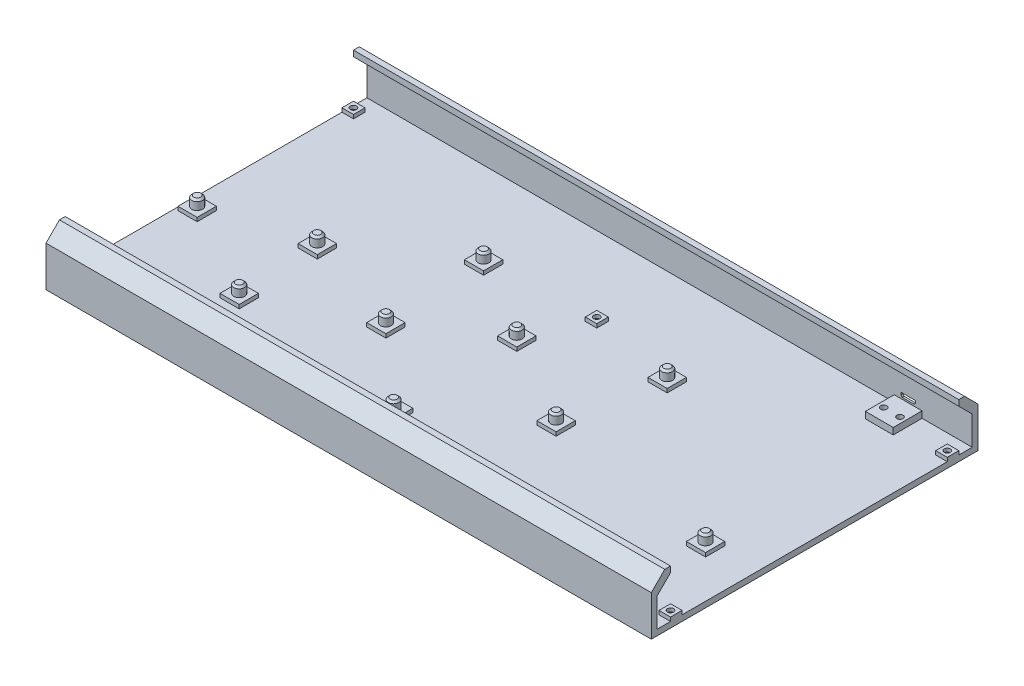
SolidWorks part; units mm, degrees
ref_plane "Front Plane" through (0, 0, 0) normal (0, 0, 1) x (1, 0, 0)
ref_plane "Top Plane" through (0, 0, 0) normal (0, 1, 0) x (1, 0, 0)
ref_plane "Right Plane" through (0, 0, 0) normal (1, 0, 0) x (0, 0, -1)
sketch "Sketch1" plane through (0, 0, 0) normal (0, 1, 0) x (1, 0, 0)
  line L1 (0, 0) -> (315, 0)
  line L2 (0, 0) -> (0, 150)
  line L3 (0, 150) -> (315, 150)
  line L4 (315, 0) -> (315, 150)
  line L5 (157.5, 150) -> (157.5, 0) construction
  line L6 (0, 75) -> (315, 75) construction
  line L7 (11.8793, 83.5932) -> (37.8793, 83.5932)
  line L8 (11.8793, 83.5932) -> (11.8793, 72.5932)
  line L9 (11.8793, 72.5932) -> (37.8793, 72.5932)
  line L10 (37.8793, 83.5932) -> (37.8793, 72.5932)
  line L11 (24.8793, 72.5932) -> (24.8793, 83.5932) construction
  line L12 (11.8793, 78.0932) -> (37.8793, 78.0932) construction
  line L17 (114.9071, 89.45) -> (181.1755, 89.45) construction
  line L18 (65.6251, 144.4154) -> (205.6251, 144.4154)
  line L42 (260.2509, 144.4154) -> (285.2509, 144.4154)
  line L43 (234.1707, 144.4154) -> (259.1707, 144.4154)
  line L44 (234.1707, 144.4154) -> (234.1707, 52.4154)
  line L45 (234.1707, 52.4154) -> (259.1707, 52.4154)
  line L46 (259.1707, 144.4154) -> (259.1707, 52.4154)
  line L47 (246.6707, 52.4154) -> (246.6707, 144.4154) construction
  line L48 (234.1707, 98.4154) -> (259.1707, 98.4154) construction
  line L49 (260.2509, 144.4154) -> (260.2509, 52.4154)
  line L50 (260.2509, 52.4154) -> (285.2509, 52.4154)
  line L51 (285.2509, 144.4154) -> (285.2509, 52.4154)
  line L52 (287.1734, 144.4154) -> (312.1734, 144.4154)
  line L53 (287.1734, 144.4154) -> (287.1734, 52.4154)
  line L54 (287.1734, 52.4154) -> (312.1734, 52.4154)
  line L55 (312.1734, 144.4154) -> (312.1734, 52.4154)
  line L72 (65.6251, 144.4154) -> (65.6251, 124.4154)
  line L73 (65.6251, 124.4154) -> (205.6251, 124.4154)
  line L74 (205.6251, 144.4154) -> (205.6251, 124.4154)
  line L75 (135.6251, 124.4154) -> (135.6251, 144.4154) construction
  line L76 (65.6251, 134.4154) -> (205.6251, 134.4154) construction
  line L81 (65.688, 113.6965) -> (85.688, 113.6965)
  line L82 (65.688, 113.6965) -> (65.688, 33.6965)
  line L83 (10.3843, 23.9694) -> (90.3843, 23.9694)
  line L84 (10.3843, 23.9694) -> (10.3843, 3.9694)
  line L85 (10.3843, 3.9694) -> (90.3843, 3.9694)
  line L86 (90.3843, 23.9694) -> (90.3843, 3.9694)
  line L87 (50.3843, 3.9694) -> (50.3843, 23.9694) construction
  line L88 (10.3843, 13.9694) -> (90.3843, 13.9694) construction
  line L89 (65.688, 33.6965) -> (85.688, 33.6965)
  line L90 (85.688, 113.6965) -> (85.688, 33.6965)
  line L91 (75.688, 33.6965) -> (75.688, 113.6965) construction
  line L92 (65.688, 73.6965) -> (85.688, 73.6965) construction
  line L93 (205.3895, 44.9232) -> (245.3895, 44.9232)
  line L94 (205.3895, 44.9232) -> (205.3895, 4.9232)
  line L95 (205.3895, 4.9232) -> (245.3895, 4.9232)
  line L96 (245.3895, 44.9232) -> (245.3895, 4.9232)
  line L97 (225.3895, 4.9232) -> (225.3895, 44.9232) construction
  line L98 (205.3895, 24.9232) -> (245.3895, 24.9232) construction
  line L99 (245.3895, 44.9232) -> (265.3895, 44.9232)
  line L100 (245.3895, 44.9232) -> (245.3895, 24.9232)
  line L101 (245.3895, 24.9232) -> (265.3895, 24.9232)
  line L102 (265.3895, 44.9232) -> (265.3895, 24.9232)
  line L103 (255.3895, 24.9232) -> (255.3895, 44.9232) construction
  line L104 (245.3895, 34.9232) -> (265.3895, 34.9232) construction
  line L105 (181.1755, 89.45) -> (181.1755, 24.3783) construction
  line L106 (181.1755, 24.3783) -> (114.9071, 24.3783) construction
  line L107 (33.5208, 117.195) -> (33.5208, 48.1962) construction
  line L109 (273.3018, 34.1392) -> (307.3018, 34.1392)
  line L110 (273.3018, 34.1392) -> (273.3018, 8.1392)
  line L111 (273.3018, 8.1392) -> (307.3018, 8.1392)
  line L112 (307.3018, 34.1392) -> (307.3018, 8.1392)
  line L113 (290.3018, 8.1392) -> (290.3018, 34.1392) construction
  line L114 (273.3018, 21.1392) -> (307.3018, 21.1392) construction
  line L115 (117.5413, 65.9142) -> (178.5413, 65.9142)
  line L116 (117.5413, 65.9142) -> (117.5413, 47.9142)
  line L117 (117.5413, 47.9142) -> (178.5413, 47.9142)
  line L118 (178.5413, 65.9142) -> (178.5413, 47.9142)
  line L119 (148.0413, 47.9142) -> (148.0413, 65.9142) construction
  line L120 (117.5413, 56.9142) -> (178.5413, 56.9142) construction
  line L121 (5.8793, 85.7294) -> (45.8793, 85.7294)
  line L122 (5.8793, 85.7294) -> (5.8793, 70.457)
  line L123 (5.8793, 70.457) -> (45.8793, 70.457)
  line L124 (45.8793, 85.7294) -> (45.8793, 70.457)
  line L125 (25.8793, 70.457) -> (25.8793, 85.7294) construction
  line L126 (5.8793, 78.0932) -> (45.8793, 78.0932) construction
  circle A0 centre (33.5208, 117.195) radius 27.5
  circle A1 centre (33.5208, 48.1962) radius 20
  circle A2 centre (114.9071, 24.3783) radius 20
  circle A3 centre (114.9071, 89.45) radius 20
  circle A4 centre (181.1755, 24.3783) radius 20
  circle A5 centre (181.1755, 89.45) radius 20
  point P38 (148.0413, 56.9142)
  point P42 (148.0413, 89.45)
  point P56 (181.1755, 56.9142)
  point P57 (25.8793, 78.0932)
  point P195 (24.8793, 78.0932)
  point P224 (290.3018, 21.1392)
  point P252 (246.6707, 98.4154)
  point P259 (225.3895, 24.9232)
  point P417 (255.3895, 34.9232)
  point P438 (75.688, 73.6965)
  point P456 (157.5, 75)
  point P559 (50.3843, 13.9694)
  point P704 (135.6251, 134.4154)
  dimension "D3" = 55
  dimension "D6" = 40
  dimension "D1" = 150
  dimension "D2" = 315
  dimension "D4" = 26
  dimension "D5" = 11
  dimension "D7" = 20
  dimension "D8" = 140
  dimension "D9" = 25
  dimension "D10" = 92
  dimension "D11" = 20
  dimension "D12" = 80
  dimension "D13" = 20
  dimension "D14" = 80
  dimension "D15" = 40
  dimension "D16" = 40
  dimension "D17" = 20
  dimension "D18" = 34
  dimension "D19" = 26
  dimension "D20" = 61
  dimension "D21" = 18
  dimension "D22" = 6
  dimension "D23" = 8
  dimension "D24" = 25
  dimension "D25" = 25
sketch "Sketch2" plane through (0, 0, 0) normal (0, 1, 0) x (1, 0, 0)
  line L1 (0, 150) -> (6, 150)
  line L2 (0, 150) -> (0, 144)
  line L3 (0, 144) -> (6, 144)
  line L4 (6, 150) -> (6, 144)
  line L5 (3, 144) -> (3, 150) construction
  line L6 (0, 147) -> (6, 147) construction
  line L8 (0, 6) -> (6, 6)
  line L9 (0, 6) -> (0, 0)
  line L10 (0, 0) -> (6, 0)
  line L11 (6, 6) -> (6, 0)
  line L12 (3, 0) -> (3, 6) construction
  line L13 (0, 3) -> (6, 3) construction
  line L25 (157.5848, 119.0301) -> (163.5848, 119.0301)
  line L26 (157.5848, 119.0301) -> (157.5848, 113.0301)
  line L31 (157.5848, 113.0301) -> (163.5848, 113.0301)
  line L32 (163.5848, 119.0301) -> (163.5848, 113.0301)
  line L37 (160.5848, 113.0301) -> (160.5848, 119.0301) construction
  line L38 (157.5848, 116.0301) -> (163.5848, 116.0301) construction
  line L43 (143.8527, 27.0473) -> (153.8527, 27.0473)
  line L44 (143.8527, 27.0473) -> (143.8527, 17.0473)
  line L49 (143.8527, 17.0473) -> (153.8527, 17.0473)
  line L50 (153.8527, 27.0473) -> (153.8527, 17.0473)
  line L55 (148.8527, 17.0473) -> (148.8527, 27.0473) construction
  line L56 (143.8527, 22.0473) -> (153.8527, 22.0473) construction
  line L68 (146.1081, 11.4408) -> (152.1081, 11.4408)
  line L73 (146.1081, 11.4408) -> (146.1081, 5.4408)
  line L74 (103.2441, 63.6402) -> (113.2441, 63.6402)
  line L75 (309, 6) -> (315, 6)
  line L76 (309, 6) -> (309, 0)
  line L77 (309, 0) -> (315, 0)
  line L78 (315, 6) -> (315, 0)
  line L79 (312, 0) -> (312, 6) construction
  line L80 (309, 3) -> (315, 3) construction
  line L85 (103.2441, 63.6402) -> (103.2441, 53.6402)
  line L86 (103.2441, 53.6402) -> (113.2441, 53.6402)
  line L87 (309, 150) -> (315, 150)
  line L88 (309, 150) -> (309, 144)
  line L89 (309, 144) -> (315, 144)
  line L90 (315, 150) -> (315, 144)
  line L91 (312, 144) -> (312, 150) construction
  line L92 (309, 147) -> (315, 147) construction
  line L93 (113.2441, 63.6402) -> (113.2441, 53.6402)
  line L94 (108.2441, 53.6402) -> (108.2441, 63.6402) construction
  line L95 (103.2441, 58.6402) -> (113.2441, 58.6402) construction
  line L96 (49.7601, 81.4098) -> (59.7601, 81.4098)
  line L97 (49.7601, 81.4098) -> (49.7601, 71.4098)
  line L98 (49.7601, 71.4098) -> (59.7601, 71.4098)
  line L99 (59.7601, 81.4098) -> (59.7601, 71.4098)
  line L100 (54.7601, 71.4098) -> (54.7601, 81.4098) construction
  line L101 (49.7601, 76.4098) -> (59.7601, 76.4098) construction
  line L102 (51.8887, 38.6479) -> (61.8887, 38.6479)
  line L103 (51.8887, 38.6479) -> (51.8887, 28.6479)
  line L104 (51.8887, 28.6479) -> (61.8887, 28.6479)
  line L105 (61.8887, 38.6479) -> (61.8887, 28.6479)
  line L106 (56.8887, 28.6479) -> (56.8887, 38.6479) construction
  line L107 (51.8887, 33.6479) -> (61.8887, 33.6479) construction
  line L108 (1.6875, 66.969) -> (11.6875, 66.969)
  line L109 (1.6875, 66.969) -> (1.6875, 56.969)
  line L110 (1.6875, 56.969) -> (11.6875, 56.969)
  line L111 (11.6875, 66.969) -> (11.6875, 56.969)
  line L112 (6.6875, 56.969) -> (6.6875, 66.969) construction
  line L113 (1.6875, 61.969) -> (11.6875, 61.969) construction
  line L114 (100.3283, 117.374) -> (110.3283, 117.374)
  line L115 (100.3283, 117.374) -> (100.3283, 107.374)
  line L116 (100.3283, 107.374) -> (110.3283, 107.374)
  line L117 (110.3283, 117.374) -> (110.3283, 107.374)
  line L118 (105.3283, 107.374) -> (105.3283, 117.374) construction
  line L119 (100.3283, 112.374) -> (110.3283, 112.374) construction
  line L120 (191.7316, 63.7001) -> (201.7316, 63.7001)
  line L121 (191.7316, 63.7001) -> (191.7316, 53.7001)
  line L122 (191.7316, 53.7001) -> (201.7316, 53.7001)
  line L123 (201.7316, 63.7001) -> (201.7316, 53.7001)
  line L124 (196.7316, 53.7001) -> (196.7316, 63.7001) construction
  line L125 (191.7316, 58.7001) -> (201.7316, 58.7001) construction
  line L130 (146.1081, 5.4408) -> (152.1081, 5.4408)
  line L131 (152.1081, 11.4408) -> (152.1081, 5.4408)
  line L132 (255.4879, 16.7818) -> (265.4879, 16.7818)
  line L133 (255.4879, 16.7818) -> (255.4879, 6.7818)
  line L134 (255.4879, 6.7818) -> (265.4879, 6.7818)
  line L135 (265.4879, 16.7818) -> (265.4879, 6.7818)
  line L136 (260.4879, 6.7818) -> (260.4879, 16.7818) construction
  line L137 (255.4879, 11.7818) -> (265.4879, 11.7818) construction
  line L138 (285.0588, 48.1735) -> (295.0588, 48.1735)
  line L139 (285.0588, 48.1735) -> (285.0588, 38.1735)
  line L140 (285.0588, 38.1735) -> (295.0588, 38.1735)
  line L141 (295.0588, 48.1735) -> (295.0588, 38.1735)
  line L142 (290.0588, 38.1735) -> (290.0588, 48.1735) construction
  line L143 (285.0588, 43.1735) -> (295.0588, 43.1735) construction
  line L144 (143.296, 91.7052) -> (153.296, 91.7052)
  line L145 (143.296, 91.7052) -> (143.296, 81.7052)
  line L146 (143.296, 81.7052) -> (153.296, 81.7052)
  line L147 (153.296, 91.7052) -> (153.296, 81.7052)
  line L148 (148.296, 81.7052) -> (148.296, 91.7052) construction
  line L149 (143.296, 86.7052) -> (153.296, 86.7052) construction
  line L150 (201.1129, 112.1386) -> (211.1129, 112.1386)
  line L151 (201.1129, 112.1386) -> (201.1129, 102.1386)
  line L152 (201.1129, 102.1386) -> (211.1129, 102.1386)
  line L153 (211.1129, 112.1386) -> (211.1129, 102.1386)
  line L154 (206.1129, 102.1386) -> (206.1129, 112.1386) construction
  line L155 (201.1129, 107.1386) -> (211.1129, 107.1386) construction
  line L156 (149.1081, 5.4408) -> (149.1081, 11.4408) construction
  line L157 (146.1081, 8.4408) -> (152.1081, 8.4408) construction
  circle A0 centre (3, 147) radius 1.6
  circle A1 centre (3, 3) radius 1.6
  circle A12 centre (312, 3) radius 1.6
  circle A14 centre (312, 147) radius 1.6
  circle A16 centre (160.5848, 116.0301) radius 1.6
  circle A17 centre (148.8527, 22.0473) radius 3
  circle A19 centre (108.2441, 58.6402) radius 3
  circle A20 centre (54.7601, 76.4098) radius 3
  circle A21 centre (56.8887, 33.6479) radius 3
  circle A22 centre (6.6875, 61.969) radius 3
  circle A23 centre (105.3283, 112.374) radius 3
  circle A24 centre (196.7316, 58.7001) radius 3
  circle A26 centre (260.4879, 11.7818) radius 3
  circle A27 centre (290.0588, 43.1735) radius 3
  circle A28 centre (148.296, 86.7052) radius 3
  circle A29 centre (206.1129, 107.1386) radius 3
  circle A30 centre (149.1081, 8.4408) radius 1.6
  dimension "D1" = 3.2
  dimension "D4" = 3.2
  dimension "D6" = 3.2
  dimension "D8" = 3.2
  dimension "D9" = 3.2
  dimension "D12" = 6
  dimension "D15" = 6
  dimension "D18" = 3.2
  dimension "D2" = 6
  dimension "D3" = 6
  dimension "D5" = 6
  dimension "D7" = 6
  dimension "D10" = 6
  dimension "D11" = 6
  dimension "D13" = 10
  dimension "D14" = 10
  dimension "D16" = 10
  dimension "D17" = 10
  dimension "D19" = 6
sketch "Sketch3" plane through (0, 0, 0) normal (0, 1, 0) x (1, 0, 0)
  line L0 (0, 0) -> (0, 150) construction
  line L1 (0, 160) -> (315, 160)
  line L2 (0, 160) -> (0, -10)
  line L3 (0, -10) -> (315, -10)
  line L4 (315, 160) -> (315, -10)
  line L5 (157.5, -10) -> (157.5, 160) construction
  line L6 (0, 75) -> (315, 75) construction
  line L7 (315, 0) -> (315, 150) construction
  line L8 (0, 150) -> (315, 150) construction
  line L9 (0, 0) -> (315, 0) construction
  point P408 (157.5, 75)
  dimension "D1" = 10
  dimension "D2" = 10
extrude "Boss-Extrude1" add sketch "Sketch3" along normal blind 3
sketch "Sketch5" plane through (0, 3, 0) normal (0, 1, 0) x (1, 0, 0)
  line L1 (0, 150) -> (6, 150)
  line L2 (0, 150) -> (0, 144)
  line L3 (0, 144) -> (6, 144)
  line L4 (6, 150) -> (6, 144)
  line L5 (3, 144) -> (3, 150) construction
  line L6 (0, 147) -> (6, 147) construction
  line L7 (6, 0) -> (0, 0)
  line L8 (6, 0) -> (6, 6)
  line L9 (6, 6) -> (0, 6)
  line L10 (0, 0) -> (0, 6)
  line L11 (3, 6) -> (3, 0) construction
  line L12 (6, 3) -> (0, 3) construction
  line L13 (1.6875, 66.969) -> (11.6875, 66.969)
  line L14 (1.6875, 66.969) -> (1.6875, 56.969)
  line L15 (1.6875, 56.969) -> (11.6875, 56.969)
  line L16 (11.6875, 66.969) -> (11.6875, 56.969)
  line L17 (6.6875, 56.969) -> (6.6875, 66.969) construction
  line L18 (1.6875, 61.969) -> (11.6875, 61.969) construction
  line L19 (49.7601, 81.4098) -> (59.7601, 81.4098)
  line L20 (49.7601, 81.4098) -> (49.7601, 71.4098)
  line L21 (49.7601, 71.4098) -> (59.7601, 71.4098)
  line L22 (59.7601, 81.4098) -> (59.7601, 71.4098)
  line L23 (54.7601, 71.4098) -> (54.7601, 81.4098) construction
  line L24 (49.7601, 76.4098) -> (59.7601, 76.4098) construction
  line L25 (51.8887, 38.6479) -> (61.8887, 38.6479)
  line L26 (51.8887, 38.6479) -> (51.8887, 28.6479)
  line L27 (51.8887, 28.6479) -> (61.8887, 28.6479)
  line L28 (61.8887, 38.6479) -> (61.8887, 28.6479)
  line L29 (56.8887, 28.6479) -> (56.8887, 38.6479) construction
  line L30 (51.8887, 33.6479) -> (61.8887, 33.6479) construction
  line L31 (100.3283, 117.374) -> (110.3283, 117.374)
  line L32 (100.3283, 117.374) -> (100.3283, 107.374)
  line L33 (100.3283, 107.374) -> (110.3283, 107.374)
  line L34 (110.3283, 117.374) -> (110.3283, 107.374)
  line L35 (105.3283, 107.374) -> (105.3283, 117.374) construction
  line L36 (100.3283, 112.374) -> (110.3283, 112.374) construction
  line L37 (103.2441, 63.6402) -> (113.2441, 63.6402)
  line L38 (103.2441, 63.6402) -> (103.2441, 53.6402)
  line L39 (103.2441, 53.6402) -> (113.2441, 53.6402)
  line L40 (113.2441, 63.6402) -> (113.2441, 53.6402)
  line L41 (108.2441, 53.6402) -> (108.2441, 63.6402) construction
  line L42 (103.2441, 58.6402) -> (113.2441, 58.6402) construction
  line L43 (143.296, 91.7052) -> (153.296, 91.7052)
  line L44 (143.296, 91.7052) -> (143.296, 81.7052)
  line L45 (143.296, 81.7052) -> (153.296, 81.7052)
  line L46 (153.296, 91.7052) -> (153.296, 81.7052)
  line L47 (148.296, 81.7052) -> (148.296, 91.7052) construction
  line L48 (143.296, 86.7052) -> (153.296, 86.7052) construction
  line L49 (143.8527, 27.0473) -> (153.8527, 27.0473)
  line L50 (143.8527, 27.0473) -> (143.8527, 17.0473)
  line L51 (143.8527, 17.0473) -> (153.8527, 17.0473)
  line L52 (153.8527, 27.0473) -> (153.8527, 17.0473)
  line L53 (148.8527, 17.0473) -> (148.8527, 27.0473) construction
  line L54 (143.8527, 22.0473) -> (153.8527, 22.0473) construction
  line L55 (146.1081, 11.4408) -> (152.1081, 11.4408)
  line L56 (146.1081, 11.4408) -> (146.1081, 5.4408)
  line L57 (146.1081, 5.4408) -> (152.1081, 5.4408)
  line L58 (152.1081, 11.4408) -> (152.1081, 5.4408)
  line L59 (149.1081, 5.4408) -> (149.1081, 11.4408) construction
  line L60 (146.1081, 8.4408) -> (152.1081, 8.4408) construction
  line L61 (191.7316, 63.7001) -> (201.7316, 63.7001)
  line L62 (191.7316, 63.7001) -> (191.7316, 53.7001)
  line L63 (191.7316, 53.7001) -> (201.7316, 53.7001)
  line L64 (201.7316, 63.7001) -> (201.7316, 53.7001)
  line L65 (196.7316, 53.7001) -> (196.7316, 63.7001) construction
  line L66 (191.7316, 58.7001) -> (201.7316, 58.7001) construction
  line L67 (201.1129, 112.1386) -> (211.1129, 112.1386)
  line L68 (201.1129, 112.1386) -> (201.1129, 102.1386)
  line L69 (201.1129, 102.1386) -> (211.1129, 102.1386)
  line L70 (211.1129, 112.1386) -> (211.1129, 102.1386)
  line L71 (206.1129, 102.1386) -> (206.1129, 112.1386) construction
  line L72 (201.1129, 107.1386) -> (211.1129, 107.1386) construction
  line L73 (157.5848, 119.0301) -> (163.5848, 119.0301)
  line L74 (157.5848, 119.0301) -> (157.5848, 113.0301)
  line L75 (157.5848, 113.0301) -> (163.5848, 113.0301)
  line L76 (163.5848, 119.0301) -> (163.5848, 113.0301)
  line L77 (160.5848, 113.0301) -> (160.5848, 119.0301) construction
  line L78 (157.5848, 116.0301) -> (163.5848, 116.0301) construction
  line L79 (255.4879, 16.7818) -> (265.4879, 16.7818)
  line L80 (255.4879, 16.7818) -> (255.4879, 6.7818)
  line L81 (255.4879, 6.7818) -> (265.4879, 6.7818)
  line L82 (265.4879, 16.7818) -> (265.4879, 6.7818)
  line L83 (260.4879, 6.7818) -> (260.4879, 16.7818) construction
  line L84 (255.4879, 11.7818) -> (265.4879, 11.7818) construction
  line L85 (285.0588, 48.1735) -> (295.0588, 48.1735)
  line L86 (285.0588, 48.1735) -> (285.0588, 38.1735)
  line L87 (285.0588, 38.1735) -> (295.0588, 38.1735)
  line L88 (295.0588, 48.1735) -> (295.0588, 38.1735)
  line L89 (290.0588, 38.1735) -> (290.0588, 48.1735) construction
  line L90 (285.0588, 43.1735) -> (295.0588, 43.1735) construction
  line L91 (309, 150) -> (315, 150)
  line L92 (309, 150) -> (309, 144)
  line L93 (309, 144) -> (315, 144)
  line L94 (315, 150) -> (315, 144)
  line L95 (312, 144) -> (312, 150) construction
  line L96 (309, 147) -> (315, 147) construction
  line L97 (309, 6) -> (315, 6)
  line L98 (309, 6) -> (309, 0)
  line L99 (309, 0) -> (315, 0)
  line L100 (315, 6) -> (315, 0)
  line L101 (312, 0) -> (312, 6) construction
  line L102 (309, 3) -> (315, 3) construction
  point P100 (3, 3)
  point P116 (3, 147)
  point P146 (54.7601, 76.4098)
  point P147 (149.1081, 8.4408)
  point P161 (312, 147)
  point P168 (260.4879, 11.7818)
  point P179 (105.3283, 112.374)
  point P181 (160.5848, 116.0301)
  point P204 (148.296, 86.7052)
  point P218 (6.6875, 61.969)
  point P224 (56.8887, 33.6479)
  point P242 (108.2441, 58.6402)
  point P271 (290.0588, 43.1735)
  point P285 (196.7316, 58.7001)
  point P292 (148.8527, 22.0473)
  point P309 (206.1129, 107.1386)
  point P320 (312, 3)
extrude "Boss-Extrude2" add sketch "Sketch5" along normal blind 2
sketch "Sketch6" plane through (0, 0, 0) normal (0, 1, 0) x (1, 0, 0)
  line L0 (160.5848, 113.0301) -> (160.5848, 119.0301) construction
  circle A0 centre (3, 147) radius 2.65
  circle A1 centre (3, 3) radius 2.65
  circle A2 centre (149.1081, 8.4408) radius 2.65
  circle A3 centre (160.5848, 116.0301) radius 2.65
  circle A4 centre (312, 3) radius 2.65
  circle A5 centre (312, 147) radius 2.65
  dimension "D1" = 5.3
  dimension "D2" = 5.3
  dimension "D3" = 5.3
  dimension "D4" = 5.3
  dimension "D5" = 5.3
  dimension "D6" = 5.3
extrude "Cut-Extrude1" cut sketch "Sketch6" along normal blind 3.2
sketch "Sketch7" plane through (0, 0, 0) normal (0, 1, 0) x (1, 0, 0)
  circle A0 centre (3, 147) radius 1.6
  circle A1 centre (312, 147) radius 1.6 construction
  circle A2 centre (312, 3) radius 1.6 construction
  circle A3 centre (149.1081, 8.4408) radius 1.6 construction
  circle A4 centre (160.5848, 116.0301) radius 1.6 construction
  circle A5 centre (3, 3) radius 1.6 construction
  circle A6 centre (312, 147) radius 1.6
  circle A7 centre (312, 3) radius 1.6
  circle A8 centre (149.1081, 8.4408) radius 1.6
  circle A9 centre (160.5848, 116.0301) radius 1.6
  circle A10 centre (3, 3) radius 1.6
extrude "Cut-Extrude2" cut sketch "Sketch7" along normal through all
sketch "Sketch8" plane through (0, 0, 0) normal (0, 1, 0) x (1, 0, 0)
  line L0 (1.6875, 61.969) -> (11.6875, 61.969) construction
  line L1 (103.2441, 58.6402) -> (113.2441, 58.6402) construction
  line L2 (105.3283, 107.374) -> (105.3283, 117.374) construction
  line L3 (148.296, 81.7052) -> (148.296, 91.7052) construction
  line L4 (201.1129, 107.1386) -> (211.1129, 107.1386) construction
  line L5 (196.7316, 53.7001) -> (196.7316, 63.7001) construction
  line L6 (148.8527, 17.0473) -> (148.8527, 27.0473) construction
  line L7 (255.4879, 11.7818) -> (265.4879, 11.7818) construction
  circle A0 centre (6.6875, 61.969) radius 2.8
  circle A1 centre (6.6875, 61.969) radius 3 construction
  circle A2 centre (54.7601, 76.4098) radius 2.8
  circle A3 centre (56.8887, 33.6479) radius 2.8
  circle A4 centre (108.2441, 58.6402) radius 2.8
  circle A5 centre (105.3283, 112.374) radius 2.8
  circle A6 centre (148.296, 86.7052) radius 2.8
  circle A7 centre (206.1129, 107.1386) radius 2.8
  circle A8 centre (196.7316, 58.7001) radius 2.8
  circle A9 centre (148.8527, 22.0473) radius 2.8
  circle A10 centre (260.4879, 11.7818) radius 2.8
  circle A11 centre (290.0588, 43.1735) radius 2.8
  dimension "D1" = 0.2
extrude "Boss-Extrude3" add sketch "Sketch8" along normal blind 10
chamfer "Chamfer1" distance 1 angle 45 11 edges at (290.0588, 10, -40.3735) (260.4879, 10, -8.9818) (206.1129, 10, -104.3386) (196.7316, 10, -55.9001) (148.8527, 10, -19.2473) (148.296, 10, -83.9052) (108.2441, 10, -55.8402) (105.3283, 10, -109.574) (56.8887, 10, -30.8479) (54.7601, 10, -73.6098) (6.6875, 10, -59.169)
sketch "Sketch9" plane through (0, 0, 0) normal (0, 1, 0) x (1, 0, 0)
  line L1 (0, 160) -> (315, 160)
  line L2 (0, 160) -> (0, 157)
  line L3 (0, 157) -> (315, 157)
  line L4 (315, 160) -> (315, 157)
  line L5 (157.5, 157) -> (157.5, 160) construction
  line L6 (0, 158.5) -> (315, 158.5) construction
  line L7 (315, -10) -> (315, 0) construction
  line L8 (0, -10) -> (315, -10)
  line L9 (0, -10) -> (0, -7)
  line L10 (0, -7) -> (315, -7)
  line L11 (315, -10) -> (315, -7)
  line L12 (157.5, -7) -> (157.5, -10) construction
  line L13 (0, -8.5) -> (315, -8.5) construction
  point P228 (157.5, 158.5)
  point P264 (157.5, -8.5)
  dimension "D1" = 3
  dimension "D2" = 3
extrude "Boss-Extrude4" add sketch "Sketch9" along normal blind 28
sketch "Sketch10" plane through (0, 28, 0) normal (0, 1, 0) x (1, 0, 0)
  line L0 (315, 150) -> (315, 157) construction
  line L1 (0, 160) -> (315, 160)
  line L2 (0, 160) -> (0, 150)
  line L3 (0, 150) -> (315, 150)
  line L4 (315, 160) -> (315, 150)
  line L5 (157.5, 150) -> (157.5, 160) construction
  line L6 (0, 155) -> (315, 155) construction
  line L8 (315, -10) -> (0, -10)
  line L9 (315, -10) -> (315, 0)
  line L10 (315, 0) -> (0, 0)
  line L11 (0, -10) -> (0, 0)
  line L12 (157.5, 0) -> (157.5, -10) construction
  line L13 (315, -5) -> (0, -5) construction
  point P256 (157.5, 155)
  point P740 (157.5, -5)
extrude "Boss-Extrude5" add sketch "Sketch10" against normal blind 3
chamfer "Chamfer2" distance 7 angle 45 4 edges at (157.5, 28, 10) (157.5, 25, 7) (157.5, 28, -160) (157.5, 25, -157)
sketch "Sketch11" plane through (0, 0, -160) normal (0, 0, -1) x (-1, 0, 0)
  line L0 (-281.645, 9.2892) -> (-281.645, 4.732) construction
  line L1 (-277.845, 9.2892) -> (-285.445, 9.2892)
  line L2 (-285.445, 9.2892) -> (-285.445, 7.9892)
  line L3 (-285.445, 7.9892) -> (-284.745, 7.2892)
  line L4 (-284.745, 7.2892) -> (-278.545, 7.2892)
  line L5 (-277.845, 7.9892) -> (-278.545, 7.2892)
  line L6 (-277.845, 9.2892) -> (-277.845, 7.9892)
  point P7 (-281.645, 7.2892)
  dimension "D1" = 3.8
  dimension "D2" = 1.3
  dimension "D3" = 2
  dimension "D4" = 135
extrude "Cut-Extrude3" cut sketch "Sketch11" against normal blind 22 contours L1 L2 L3 L4 L5 L6
sketch "Sketch12" plane through (0, 0, -160) normal (0, 0, -1) x (-1, 0, 0)
  line L0 (-281.645, 9.2892) -> (-281.645, 4.6946) construction
  line L1 (-277.845, 9.2892) -> (-285.445, 9.2892) construction
  line L2 (-1.6875, 3) -> (-11.6875, 3) construction
  line L3 (-274.395, 3) -> (-288.895, 3)
  line L4 (-274.395, 3) -> (-274.395, 6.3892)
  line L5 (-274.395, 6.3892) -> (-288.895, 6.3892)
  line L6 (-288.895, 3) -> (-288.895, 6.3892)
  line L7 (-281.645, 6.3892) -> (-281.645, 3) construction
  line L8 (-274.395, 4.6946) -> (-288.895, 4.6946) construction
  dimension "D1" = 14.5
  dimension "D2" = 2.9
extrude "Boss-Extrude6" add sketch "Sketch12" against normal blind 18
sketch "Sketch13" plane through (0, 6.3892, 0) normal (0, 1, 0) x (1, 0, 0)
  line L0 (274.395, 148.4873) -> (288.895, 148.4873) construction
  line L1 (274.395, 142) -> (274.395, 157) construction
  line L2 (288.895, 142) -> (288.895, 157) construction
  line L3 (281.645, 148.4873) -> (281.645, 143.7714) construction
  circle A0 centre (277.395, 148.4873) radius 1.6
  circle A1 centre (285.895, 148.4873) radius 1.6
  dimension "D1" = 3.2
  dimension "D3" = 8.5
extrude "Cut-Extrude4" cut sketch "Sketch13" against normal up to surface (3.3892 mm away) up to face at (178.1908, 3, -87.4167)
sketch "Sketch14" plane through (0, 0, -160) normal (0, 0, -1) x (-1, 0, 0)
  line L0 (-281.645, 9.2892) -> (-281.645, 7.2892) construction
  line L1 (-277.845, 9.2892) -> (-285.445, 9.2892) construction
  line L2 (-284.745, 7.2892) -> (-278.545, 7.2892) construction
  line L4 (-288.645, 12.2892) -> (-274.645, 12.2892)
  line L5 (-288.645, 12.2892) -> (-288.645, 4.2892)
  line L6 (-288.645, 4.2892) -> (-274.645, 4.2892)
  line L7 (-274.645, 12.2892) -> (-274.645, 4.2892)
  line L8 (-281.645, 4.2892) -> (-281.645, 12.2892) construction
  line L9 (-288.645, 8.2892) -> (-274.645, 8.2892) construction
  point P6 (-281.645, 8.2892)
  dimension "D1" = 14
  dimension "D2" = 8
extrude "Cut-Extrude5" cut sketch "Sketch14" against normal blind 2
sketch "Sketch15" plane through (0, 3, 0) normal (0, 1, 0) x (1, 0, 0)
  circle A0 centre (33.5208, 48.1962) radius 7.5
  circle A1 centre (114.9071, 89.45) radius 7.5
  circle A2 centre (181.1755, 89.45) radius 7.5
  circle A3 centre (181.1755, 24.3783) radius 7.5
  circle A4 centre (114.9071, 24.3783) radius 7.5
  dimension "D1" = 15
extrude "Boss-Extrude7" [suppressed] add sketch "Sketch15" along normal blind 11
sketch "Sketch18" plane through (0, 0, 0) normal (0, 1, 0) x (1, 0, 0)
  line L0 (157.5, 150) -> (157.5, 0) construction
  line L1 (0, 150) -> (315, 150) construction
  line L2 (315, 0) -> (0, 0) construction
  line L3 (111.2441, 83.0168) -> (203.7559, 83.0168) construction
  line L8 (157.5, 55.8537) -> (157.5, 94.1463) construction
  line L9 (116.8993, 75) -> (198.1007, 75) construction
  line L14 (157.5, 54.3537) -> (157.5, 95.6463) construction
  line L15 (115.3993, 75) -> (199.6007, 75) construction
  text T0 "NEPTUNE MIDI\r\nDESIGNED BY JZ\r\n2021 Sept in California" font "Century Gothic" height 6
  point P6 (157.5, 75)
  point P10 (157.5, 75)
  point P19 (157.5, 83.0168)
extrude "Cut-Extrude6" [suppressed] cut sketch "Sketch18" along normal blind 1
sketch "Sketch19" plane through (0, 0, 0) normal (0, 1, 0) x (1, 0, 0)
  line L0 (157.5, 150) -> (157.5, 0) construction
  line L1 (0, 150) -> (315, 150) construction
  line L2 (315, 0) -> (0, 0) construction
  line L4 (106.7795, 99.0587) -> (208.2205, 99.0587)
  line L5 (106.7795, 99.0587) -> (106.7795, 50.9413)
  line L6 (106.7795, 50.9413) -> (208.2205, 50.9413)
  line L7 (208.2205, 99.0587) -> (208.2205, 50.9413)
  line L8 (157.5, 50.9413) -> (157.5, 99.0587) construction
  line L9 (106.7795, 75) -> (208.2205, 75) construction
  line L10 (105.2795, 100.5587) -> (209.7205, 100.5587)
  line L11 (105.2795, 100.5587) -> (105.2795, 49.4413)
  line L12 (105.2795, 49.4413) -> (209.7205, 49.4413)
  line L13 (209.7205, 100.5587) -> (209.7205, 49.4413)
  line L14 (157.5, 49.4413) -> (157.5, 100.5587) construction
  line L15 (105.2795, 75) -> (209.7205, 75) construction
  point P6 (157.5, 75)
  point P10 (157.5, 75)
  dimension "D1" = 1.5
  dimension "D2" = 1.5
extrude "Cut-Extrude8" [suppressed] cut sketch "Sketch19" along normal blind 1
